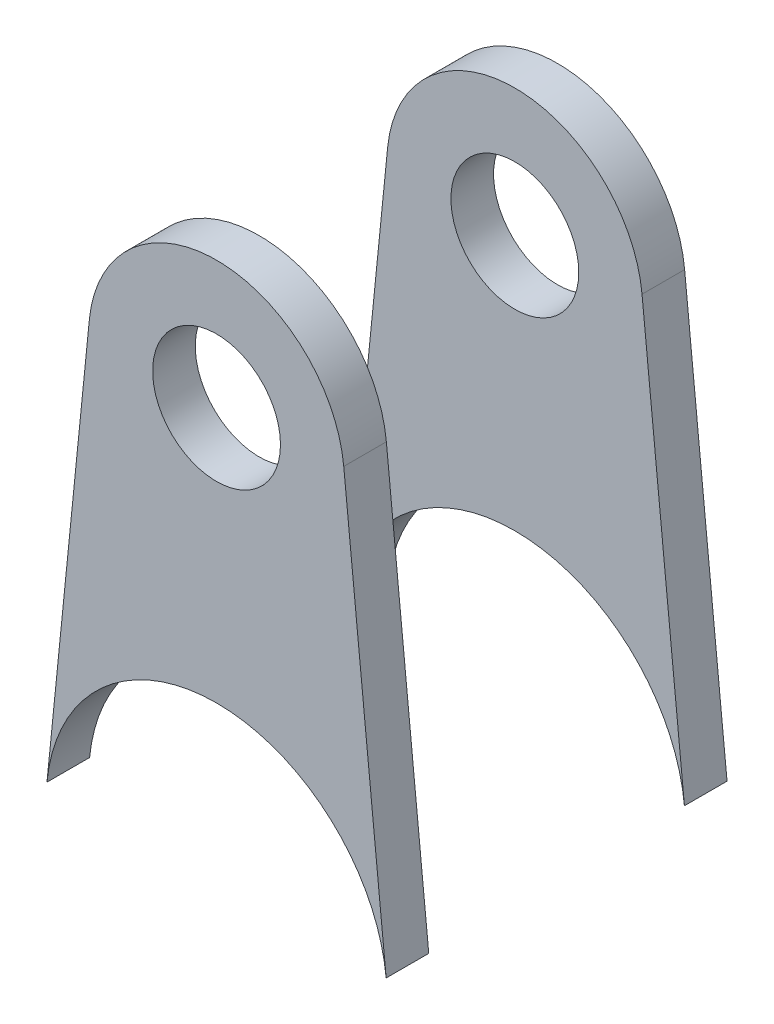
SolidWorks part; units mm, degrees
ref_plane "Front Plane" through (0, 0, 0) normal (0, 0, 1) x (1, 0, 0)
ref_plane "Top Plane" through (0, 0, 0) normal (0, 1, 0) x (1, 0, 0)
ref_plane "Right Plane" through (0, 0, 0) normal (1, 0, 0) x (0, 0, -1)
sketch "Sketch1" plane through (0, 0, 0) normal (0, 0, 1) x (1, 0, 0)
  line L0 (0, 0) -> (0, -31.75) construction
  line L1 (-9.4773, 0.9525) -> (-12.6363, -30.48)
  line L2 (9.4773, 0.9525) -> (12.6363, -30.48)
  circle A0 centre (0, 0) radius 4.7625
  circle A1 centre (0, 0) radius 9.525
  circle A2 centre (0, -31.75) radius 12.7
  dimension "D1" = 25.4
  dimension "D2" = 9.525
  dimension "D4" = 19.05
  dimension "D3" = 31.75
extrude "Boss-Extrude1" add sketch "Sketch1" against normal blind 3.175 from offset 12.7 contours A0 A1 | L0 A1 L1 A2 | A1 L0 A2 L2 region at (-6.8641, -6.2088, 0) region at (6.5277, -14.4855, 0) region at (-6.5277, -14.4855, 0)
extrude "Boss-Extrude2" add sketch "Sketch1<4>" along normal blind 3.175 from offset 12.7 separate body contours A0 A1 | A1 L0 A2 L2 | L0 A1 L1 A2 region at (-6.8641, -6.2088, 0) region at (6.5277, -14.4855, 0) region at (-6.5277, -14.4855, 0) offset against normal yes
sketch "Sketch1<4>" plane through (0, 0, 0) normal (0, 0, 1) x (1, 0, 0) same geometry as "Sketch1"
